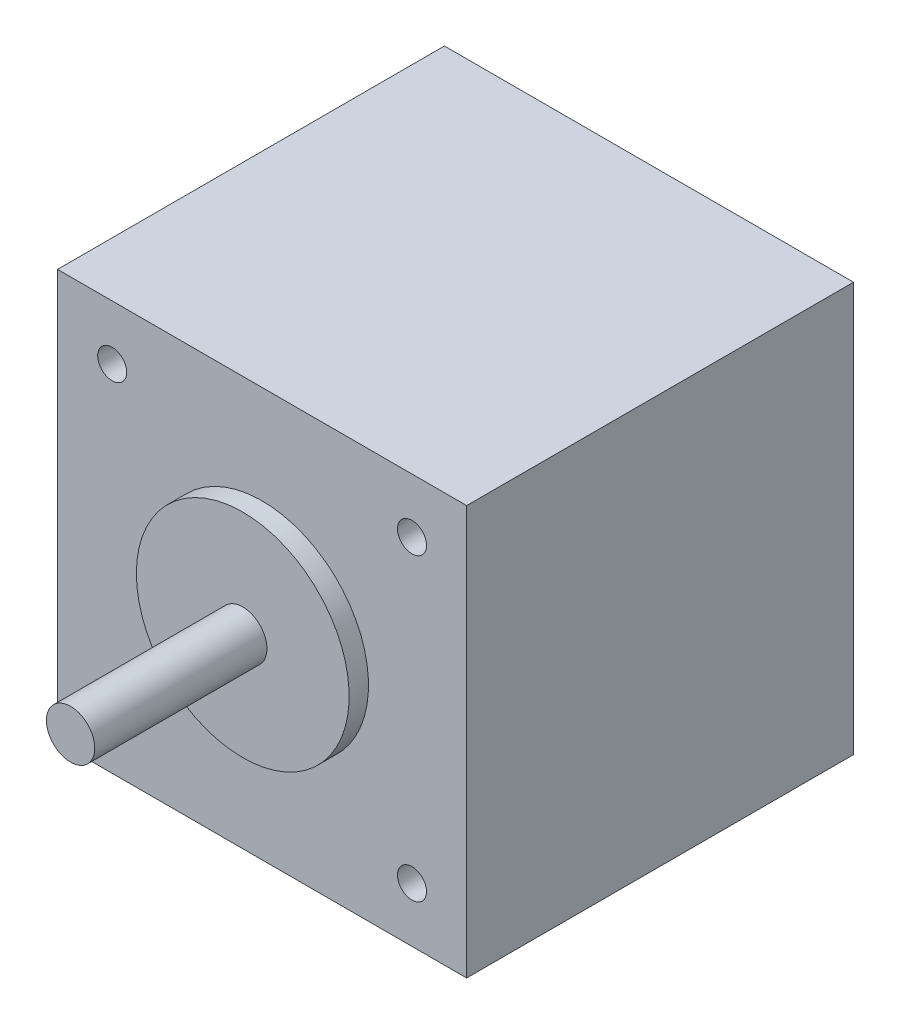
SolidWorks part; units mm, degrees
ref_plane "Спереди" through (0, 0, 0) normal (0, 0, 1) x (1, 0, 0)
ref_plane "Сверху" through (0, 0, 0) normal (0, 1, 0) x (1, 0, 0)
ref_plane "Справа" through (0, 0, 0) normal (1, 0, 0) x (0, 0, -1)
other "Configuration Table"
sketch "Эскиз1" plane through (0, 0, 0) normal (0, 0, 1) x (1, 0, 0)
  line L1 (-21.15, -21.15) -> (21.15, -21.15)
  line L2 (-21.15, -21.15) -> (-21.15, 21.15)
  line L3 (-21.15, 21.15) -> (21.15, 21.15)
  line L4 (21.15, -21.15) -> (21.15, 21.15)
  line L5 (-21.15, -21.15) -> (21.15, 21.15) construction
  line L6 (-21.15, 21.15) -> (21.15, -21.15) construction
  point P0 (0, 0)
  dimension "D1" = 42.3
  dimension "D2" = 42.3
extrude "Корпус" add sketch "Эскиз1" along normal blind 40
sketch "Эскиз2" plane through (0, 0, 0) normal (0, 0, 1) x (1, 0, 0)
  circle A0 centre (0, 0) radius 2.5
extrude "Вал_ПРЕДВ" add sketch "Эскиз2" along normal blind 59.8
sketch "Эскиз3" plane through (0, 0, 0) normal (0, 0, 1) x (1, 0, 0)
  circle A0 centre (0, 0) radius 11
  dimension "D1" = 22
extrude "Буртик_ПРЕДВ" add sketch "Эскиз3" along normal blind 42
sketch "Эскиз4" plane through (0, 0, 0) normal (0, 0, 1) x (1, 0, 0)
  circle A0 centre (0, 0) radius 8
  dimension "D1" = 16
sketch "Эскиз5" plane through (0, 0, 0) normal (0, 0, 1) x (1, 0, 0)
  circle A0 centre (-15.5, -15.5) radius 1.5
  circle A1 centre (-15.5, 15.5) radius 1.5
  circle A2 centre (15.5, -15.5) radius 1.5
  circle A3 centre (15.5, 15.5) radius 1.5
  dimension "D1" = 3
  dimension "D2" = 3
  dimension "D3" = 3
  dimension "D4" = 3
extrude "Крепеж_М3_ПРЕДВ" cut sketch "Эскиз5" against normal blind 4.5 from offset 40
equation "\"Мотор X ширина корпуса\"= 42.3"
equation "\"Мотор X высота корпуса\"= 42.3"
equation "\"Мотор X длина корпуса\"= 40"
equation "\"Мотор X вылет вала\"= 19.8"
equation "\"Мотор Y ширина корпуса\"= 42.3"
equation "\"Мотор Y высота корпуса\"= 42.3"
equation "\"Мотор Y длина корпуса\"= 48"
equation "\"Мотор Y вылет вала\"= 30"
equation "\"Мотор Z ширина корпуса\"= 42"
equation "\"Мотор Z высота корпуса\"= 42"
equation "\"Мотор Z длина корпуса\"= 40"
equation "\"Мотор Z вылет вала\"= 23"
equation "\"Мотор диаметр вала ПРЕДВ\"= 5"
equation "\"Мотор шаг крепления ПРЕДВ\"= 31"
equation "\"Мотор диаметр отверстий ПРЕДВ\"= 3"
equation "\"Мотор глубина отверстий ПРЕДВ\"= 4.5"
equation "\"Мотор диаметр буртика ПРЕДВ\"= 22"
equation "\"Мотор высота буртика ПРЕДВ\"= 2"
equation "\"Мотор диаметр шкива ПРЕДВ\"= 16"
equation "\"Мотор длина шкива ПРЕДВ\"= 12"
equation "\"Мотор отступ шкива ПРЕДВ\"= 5"
equation "\"Мотор X шаг градусов\"= 1.8"
equation "\"Мотор Y шаг градусов\"= 1.8"
equation "\"Мотор Z шаг градусов\"= 1.8"
equation "\"Мотор Y диаметр ротора\"= 25.78"
equation "\"D1@Эскиз1\" = \"Мотор X ширина корпуса\""
equation "\"D1@Корпус\" = \"Мотор X длина корпуса\""
equation "\"D1@Эскиз2\" = \"Мотор диаметр вала ПРЕДВ\""
equation "\"D1@Вал_ПРЕДВ\" = \"Мотор X длина корпуса\" + \"Мотор X вылет вала\""
equation "\"D1@Эскиз3\" = \"Мотор диаметр буртика ПРЕДВ\""
equation "\"D1@Буртик_ПРЕДВ\" = \"Мотор X длина корпуса\" + \"Мотор высота буртика ПРЕДВ\""
equation "\"D1@Эскиз4\" = \"Мотор диаметр шкива ПРЕДВ\""
equation "\"D1@Эскиз5\" = \"Мотор диаметр отверстий ПРЕДВ\""
equation "\"D2@Эскиз5\" = \"Мотор диаметр отверстий ПРЕДВ\""
equation "\"D3@Эскиз5\" = \"Мотор диаметр отверстий ПРЕДВ\""
equation "\"D4@Эскиз5\" = \"Мотор диаметр отверстий ПРЕДВ\""
equation "\"D1@Крепеж_М3_ПРЕДВ\" = \"Мотор глубина отверстий ПРЕДВ\""
equation "\"D19@Крепеж_М3_ПРЕДВ\" = \"Мотор X длина корпуса\""
equation "\"Ширина груза\"= 160"
equation "\"Глубина груза\"= 240"
equation "\"Высота груза\"= 160"
equation "\"Ширина ячейки\"= \"Ширина груза\" + 10"
equation "\"Глубина ячейки\"= \"Глубина груза\" + 10"
equation "\"Высота ячейки\"= \"Высота груза\" + 10 + 13"
equation "\"Колво ячеек ширина\"= 2"
equation "\"Колво ячеек высота\"= 2"
equation "\"Толщина стенки\" = \"Толщина тонких панелей\""
equation "\"Крепление дверцы\"= 5 "
equation "\"Ширина рейки\"= \"Толщина шестерни\""
equation "\"Высота рейки\"= 20"
equation "\"Высота пола\" = 2*\"Толщина тонких панелей\""
equation "\"Колво полозьев\"= 5"
equation "\"Отступ рейки\"= 20"
equation "\"Глубина каретки\"= \"Глубина ячейки\" + 30 + \"Мотор Y высота корпуса\" + 20 + \"Удлинение платформы по глубине\""
equation "\"Отступ шпильки\"= 26"
equation "\"Диаметр шпильки\"= 5"
equation "\"Длинна шпильки\" = (\"Высота ячейки\"+\"Толщина горизонтальных плит\"+\"Высота пола\")*\"Колво ячеек высота\"+2*(\"Толщина горизонтальных плит\"+\"Отступ рейки\")"
equation "\"Ширина пластины\" = 50"
equation "\"Высота зона выгрузки\"= \"Высота ячейки\" * 2 + \"Толщина стенки\" * 2"
equation "\"Колво выгрузки\"= 1"
equation "\"Отступ крепления мотора фиксации\" = (70-\"Толщина вертикальных стенок\")/2"
equation "\"Диаметр оси\"= 10"
equation "\"Диаметр ролика\"= 20"
equation "\"Колво роликов\"= 10"
equation "\"Шаг роликов\"= \"Диаметр ролика\" + 20"
equation "\"Ширина ячейки выгрузки\" = \"Ширина ячейки\"+\"Толщина вертикальных стенок\"+2*\"Отступ крепления мотора фиксации\""
equation "\"Длинна рейки\" = (\"Ширина ячейки\"+\"Толщина вертикальных стенок\"+\"Крепление дверцы\")*\"Колво ячеек ширина\"+\"Ширина ячейки выгрузки\"*\"Колво выгрузки\"+\"Толщина вертикальных стенок\"+2*\"Отступ крепления мотора фиксации\"-\"Крепление дверцы\"*\"Колво ячеек ширина\""
equation "\"Толщина шестерни\"= 10"
equation "\"Толщина тонких панелей\" = 6"
equation "\"Толщина вертикальных стенок\" = 6"
equation "\"Толщина горизонтальных плит\" = 6"
equation "\"Базовая высота корпуса\"= (\"Высота ячейки\"+\"Толщина тонких панелей\"+\"Высота пола\")*\"Колво ячеек высота\"+6*\"Толщина тонких панелей\"+\"Мотор X ширина корпуса\"+\"Мотор Y ширина корпуса\"+75"
equation "\"Высота корпуса\"= (\"Высота ячейки\"+\"Толщина горизонтальных плит\"+\"Высота пола\")*\"Колво ячеек высота\"+2*\"Толщина горизонтальных плит\"+4*\"Толщина тонких панелей\"+\"Мотор X ширина корпуса\"+\"Мотор Y ширина корпуса\"+75"
equation "\"Смещение центра корпуса\"= (\"Высота корпуса\"-\"Базовая высота корпуса\")/2-(\"Толщина горизонтальных плит\"-\"Толщина тонких панелей\")"
equation "\"Отметка пола\"= -\"Базовая высота корпуса\"/2+\"Толщина тонких панелей\""
equation "\"Отметка потолка\"= \"Отметка пола\"+\"Высота корпуса\"-2*\"Толщина горизонтальных плит\""
equation "\"Отметка верхней полки\"= \"Отметка потолка\"-(28+\"Толщина тонких панелей\")-\"Высота ячейки\"-\"Высота пола\""
equation "\"Отметка нижней полки\"= \"Отметка верхней полки\"-\"Высота ячейки\"-\"Высота пола\"-\"Толщина горизонтальных плит\""
